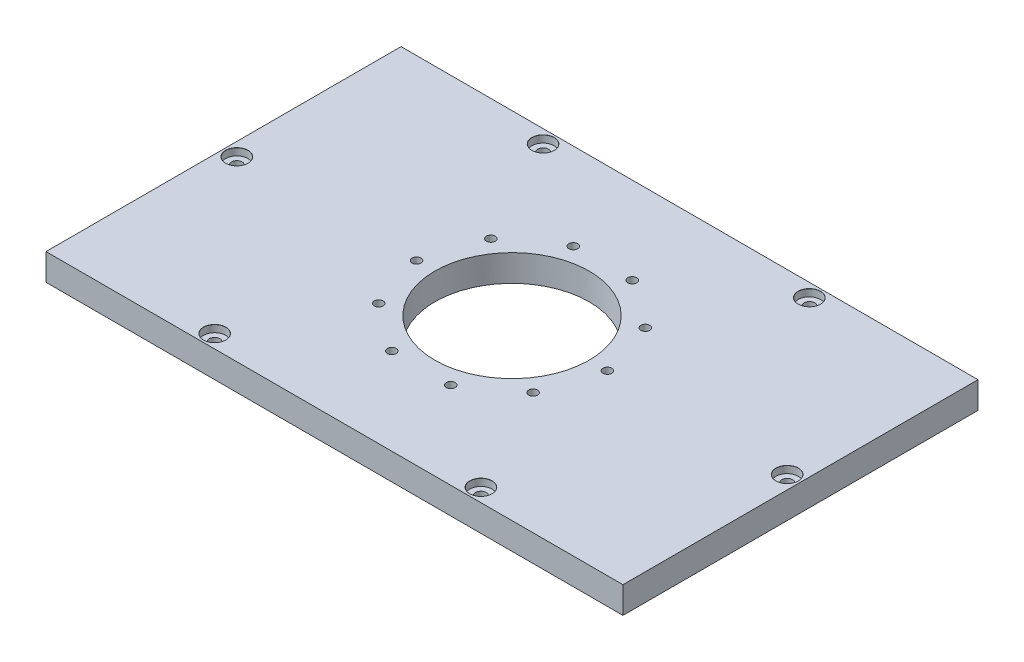
SolidWorks part; units mm, degrees
ref_plane "Ebene vorne" through (0, 0, 0) normal (0, 0, 1) x (1, 0, 0)
ref_plane "Ebene oben" through (0, 0, 0) normal (0, 1, 0) x (1, 0, 0)
ref_plane "Ebene rechts" through (0, 0, 0) normal (1, 0, 0) x (0, 0, -1)
sketch "Skizze1" plane through (0, 0, 0) normal (0, 1, 0) x (1, 0, 0)
  line L1 (0, 0) -> (130, 0)
  line L2 (0, 0) -> (0, 80)
  line L3 (0, 80) -> (130, 80)
  line L4 (130, 0) -> (130, 80)
  dimension "D1" = 80
  dimension "D2" = 130
extrude "Aufsatz-Linear austragen1" add sketch "Skizze1" along normal blind 6
hole_wizard "Ø2.4 (2.4) Durchmesser Bohrung1" positions "Skizze2" profile "Skizze3" hole size "Ø2.4" standard "DIN"
sketch "Skizze2" plane through (0, 6, 0) normal (0, 1, 0) x (1, 0, 0)
  line L0 (130, 80) -> (0, 80) construction
  line L1 (130, 0) -> (130, 80) construction
  line L2 (0, -3.3) -> (0, 3.3) construction
  line L3 (-3.3, 0) -> (3.3, 0) construction
  point P0 (35, 77)
  point P2 (95, 77)
  point P4 (127, 40)
  point P6 (95, 3)
  point P8 (35, 3)
  point P10 (3, 40)
  point P21 (133.0887, 32.8034)
  dimension "D1" = 3
  dimension "D2" = 3
  dimension "D3" = 3
  dimension "D4" = 3
  dimension "D5" = 3
  dimension "D6" = 3
  dimension "D7" = 35
  dimension "D8" = 35
  dimension "D9" = 35
  dimension "D10" = 35
  dimension "D11" = 40
  dimension "D12" = 40
sketch "Skizze3" plane through (35, 6, -77) normal (1, 0, 0) x (0, 0, 1)
  line L0 (0, 0) -> (0, 10.721)
  line L1 (0, 10.721) -> (1.2, 10)
  line L2 (1.2, 10) -> (1.2, 0.025)
  line L3 (1.2, 0.025) -> (1.225, 0)
  line L5 (1.225, 0) -> (0, 0)
  line L6 (-1.2, 0.025) -> (-1.225, 0) construction
  line L10 (0, 10.721) -> (-1.2, 10) construction
  line L11 (0, -6.35) -> (0, 107.95) construction
  dimension "Bohrerdurchmesser" = 2.4
  dimension "Bohrungstiefe" = 10
  dimension "Senkdurchmesser2 (Oben)" = 2.45
  dimension "Senkwinkel2 (Oben)" = 90
  dimension "Spitzenwinkel" = 118
hole_wizard "Stirnsenkung für M2 Flachkopfschraube mit Schlitz1" positions "Skizze6" profile "Skizze7" counterbore size "M2" standard "DIN"
sketch "Skizze6" plane through (0, 6, 0) normal (0, 1, 0) x (1, 0, 0)
  point P0 (95, 3)
  point P3 (127, 40)
  point P6 (95, 77)
  point P9 (35, 77)
  point P12 (3, 40)
  point P15 (35, 3)
sketch "Skizze7" plane through (95, 6, -3) normal (1, 0, 0) x (0, 0, 1)
  line L0 (0, 0) -> (0, 2.721)
  line L1 (0, 2.721) -> (1.2, 2)
  line L2 (1.2, 2) -> (1.2, 1.6)
  line L3 (1.2, 1.6) -> (2.5, 1.6)
  line L5 (2.5, 1.6) -> (2.5, 0.025)
  line L6 (2.5, 0.025) -> (2.525, 0)
  line L7 (2.525, 0) -> (0, 0)
  line L8 (-2.5, 0.025) -> (-2.525, 0) construction
  line L10 (0, 2.721) -> (-1.2, 2) construction
  line L11 (0, -6.35) -> (0, 107.95) construction
  dimension "Bohrerdurchmesser" = 2.4
  dimension "Bohrungstiefe" = 2
  dimension "Senkdurchmesser2" = 5
  dimension "Senktiefe2" = 1.6
  dimension "Senkdurchmesser4 (Oben)" = 5.05
  dimension "Senkwinkel2 (Oben)" = 90
  dimension "Spitzenwinkel" = 118
sketch "Skizze8" plane through (0, 6, 0) normal (0, 1, 0) x (1, 0, 0)
  line L0 (65, -24.4296) -> (65, 94.5281) construction
  line L1 (130, 0) -> (130, 80) construction
  line L3 (0, 80) -> (0, 0) construction
  line L4 (147.1504, 40) -> (-23.042, 40) construction
  line L5 (0, 0) -> (130, 0) construction
  line L6 (130, 80) -> (0, 80) construction
  circle A1 centre (47.6061, 52.6374) radius 1
  circle A2 centre (58.3561, 60.4477) radius 1
  circle A3 centre (71.6439, 60.4477) radius 1
  circle A4 centre (82.3939, 52.6374) radius 1
  circle A5 centre (86.5, 40) radius 1
  circle A6 centre (82.3939, 27.3626) radius 1
  circle A7 centre (71.6439, 19.5523) radius 1
  circle A8 centre (58.3561, 19.5523) radius 1
  circle A9 centre (47.6061, 27.3626) radius 1
  circle A10 centre (43.5, 40) radius 1
  circle A17 centre (65, 40) radius 17.3939
  point P14 (65, 40)
  dimension "D1" = 2
  dimension "D3" = 43
  dimension "D11" = 34.7877
  dimension "D2" = 10
extrude "Schnitt-Linear austragen1" cut sketch "Skizze8" against normal up to surface (6 mm away) up to face at (35, 0, -78.2)
